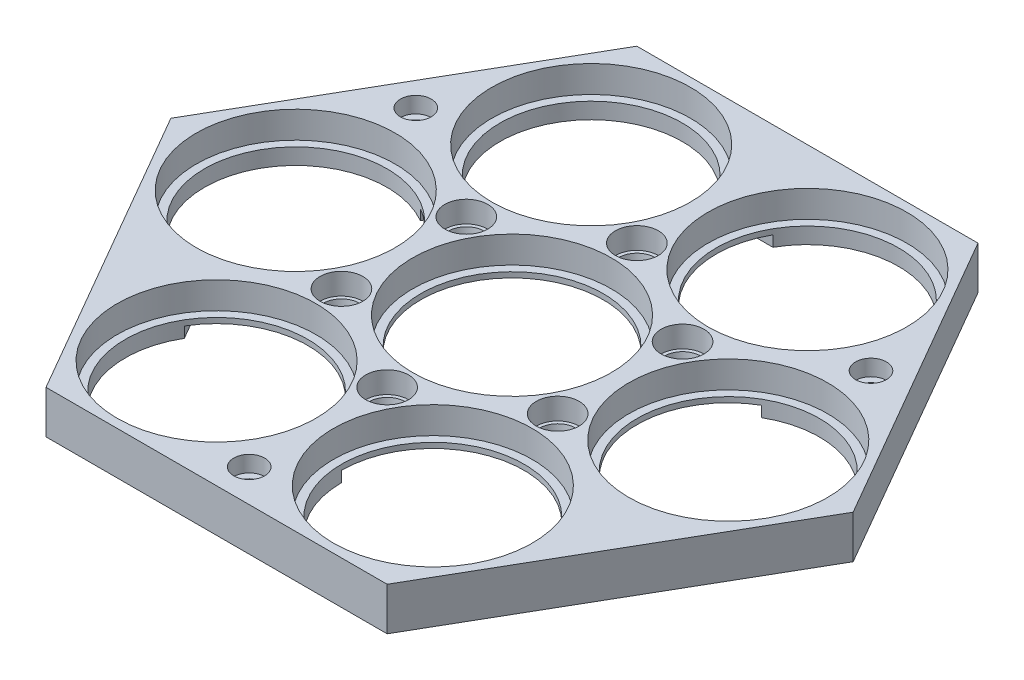
SolidWorks part; units mm, degrees
material "Malleable Cast Iron"
ref_plane "Front Plane" through (0, 0, 0) normal (0, 0, 1) x (1, 0, 0)
ref_plane "Top Plane" through (0, 0, 0) normal (0, 1, 0) x (1, 0, 0)
ref_plane "Right Plane" through (0, 0, 0) normal (1, 0, 0) x (0, 0, -1)
sketch "Sketch1" plane through (0, 0, 0) normal (0, 1, 0) x (1, 0, 0)
  line L0 (-23.3, 0) -> (-17, 0) construction
  line L1 (40.3, 0) -> (20.15, 34.9008) construction
  line L2 (20.15, 34.9008) -> (-20.15, 34.9008) construction
  line L3 (-20.15, 34.9008) -> (-40.3, 0) construction
  line L4 (-40.3, 0) -> (-20.15, -34.9008) construction
  line L5 (-20.15, -34.9008) -> (20.15, -34.9008) construction
  line L6 (20.15, -34.9008) -> (40.3, 0) construction
  line L7 (-20.15, 51.9008) -> (-20.15, 55.0508) construction
  line L8 (63.5672, 0) -> (31.7836, 55.0508)
  line L9 (31.7836, 55.0508) -> (-31.7836, 55.0508)
  line L10 (-31.7836, 55.0508) -> (-63.5672, 0)
  line L11 (-63.5672, 0) -> (-31.7836, -55.0508)
  line L12 (-31.7836, -55.0508) -> (31.7836, -55.0508)
  line L13 (31.7836, -55.0508) -> (63.5672, 0)
  line L14 (-20.15, 0) -> (-17, 0)
  circle A0 centre (0, 0) radius 17
  circle A1 centre (0, 0) radius 34.9008 construction
  circle A2 centre (-20.15, 34.9008) radius 17
  circle A3 centre (20.15, 34.9008) radius 17
  circle A4 centre (40.3, 0) radius 17
  circle A5 centre (20.15, -34.9008) radius 17
  circle A6 centre (-20.15, -34.9008) radius 17
  circle A7 centre (-40.3, 0) radius 17
  circle A8 centre (0, 0) radius 55.0508 construction
  dimension "D1" = 34
  dimension "D2" = 6.3
extrude "Boss-Extrude1" add sketch "Sketch1" along normal blind 1 contours L12 L13 L8 L9 L10 L11 A7 A6 A5 A4 A3 A2 A0 region at (46.2189, 0, 26.6845)
sketch "Sketch2" plane through (0, 1, 0) normal (0, 1, 0) x (1, 0, 0)
  line L1 (63.5672, 0) -> (31.7836, 55.0508)
  line L2 (31.7836, 55.0508) -> (-31.7836, 55.0508)
  line L3 (-31.7836, 55.0508) -> (-63.5672, 0)
  line L4 (-63.5672, 0) -> (-31.7836, -55.0508)
  line L5 (-31.7836, -55.0508) -> (31.7836, -55.0508)
  line L6 (31.7836, -55.0508) -> (63.5672, 0)
  circle A0 centre (-40.3, 0) radius 18.525
  circle A1 centre (-20.15, 34.9008) radius 18.525
  circle A2 centre (20.15, 34.9008) radius 18.525
  circle A3 centre (0, 0) radius 18.525
  circle A4 centre (40.3, 0) radius 18.525
  circle A5 centre (20.15, -34.9008) radius 18.525
  circle A6 centre (-20.15, -34.9008) radius 18.525
  circle A7 centre (0, 0) radius 55.0508 construction
  dimension "D1" = 37.05
extrude "Boss-Extrude2" add sketch "Sketch2" along normal blind 5
sketch "Sketch3" plane through (0, 6, 0) normal (0, 1, 0) x (1, 0, 0)
  line L0 (-24.2569, 9.2625) -> (-20.15, 16.3758) construction
  line L1 (-20.15, 16.3758) -> (-16.0431, 9.2625) construction
  line L2 (-16.0431, 9.2625) -> (-24.2569, 9.2625) construction
  circle A0 centre (-20.15, 11.6336) radius 4
  circle A1 centre (20.15, 11.6336) radius 4
  circle A2 centre (0, -23.2672) radius 4
  circle A3 centre (-20.15, -11.6336) radius 4
  circle A4 centre (20.15, -11.6336) radius 4
  circle A5 centre (0, 0) radius 23.2672 construction
  circle A6 centre (-40.3, 0) radius 18.525 construction
  circle A7 centre (-20.15, 34.9008) radius 18.525 construction
  circle A8 centre (0, 0) radius 18.525 construction
  circle A9 centre (0, 23.2672) radius 4
  dimension "D1" = 120
  dimension "D3" = 8
  dimension "D2" = 120
extrude "Cut-Extrude1" cut sketch "Sketch3" against normal blind 4 and the other way through all
extrude "Cut-Extrude2" cut sketch "Sketch3<2>" against normal through all draft 9 contours A0 | A1 | A2 | A3 | A4 | A9 region at (-20.15, 6, -11.6336) region at (20.15, 6, -11.6336) region at (0, 6, 23.2672) region at (-20.15, 6, 11.6336) region at (20.15, 6, 11.6336) region at (0, 6, -23.2672)
sketch "Sketch3<2>" plane through (0, 6, 0) normal (0, 1, 0) x (1, 0, 0) same geometry as "Sketch3"
sketch "Sketch4" plane through (0, 0, 0) normal (0, -1, 0) x (1, 0, 0)
  circle A0 centre (0, -23.2672) radius 4
  circle A1 centre (-20.15, 11.6336) radius 4
  circle A2 centre (20.15, 11.6336) radius 4
  circle A3 centre (0, 0) radius 23.2672 construction
  point P11 (20.15, -11.6336)
  dimension "D1" = 8
sketch "Sketch5" plane through (0, 0, 0) normal (0, -1, 0) x (1, 0, 0)
  line L0 (-63.5672, 0) -> (-31.7836, -55.0508)
  line L1 (-31.7836, -55.0508) -> (-63.5672, 0) construction
  line L3 (-28.65, -20.1784) -> (-31.8, -14.7224)
  line L4 (-63.5672, 0) -> (-57.3, 0)
  line L5 (-5.3512, -43.2672) -> (5.3512, -43.2672)
  line L6 (31.7836, -55.0508) -> (28.65, -49.6233)
  line L7 (-31.7836, -55.0508) -> (31.7836, -55.0508)
  line L8 (31.7836, 55.0508) -> (-31.7836, 55.0508)
  line L9 (-3.15, 34.9008) -> (3.15, 34.9008)
  line L10 (31.7836, 55.0508) -> (28.65, 49.6233)
  line L11 (-34.7949, 26.2679) -> (-40.1461, 16.9993)
  line L12 (-63.5672, 0) -> (-57.3, 0)
  line L13 (-31.7836, 55.0508) -> (-63.5672, 0)
  line L14 (31.7836, -55.0508) -> (63.5672, 0)
  line L15 (31.8, -14.7224) -> (28.65, -20.1784)
  line L16 (31.7836, -55.0508) -> (28.65, -49.6233)
  line L17 (40.1461, 16.9993) -> (34.7949, 26.2679)
  line L18 (31.7836, 55.0508) -> (28.65, 49.6233)
  line L19 (63.5672, 0) -> (31.7836, 55.0508)
  circle A0 centre (-20.15, -34.9008) radius 17 construction
  circle A2 centre (-40.3, 0) radius 17 construction
  arc A3 (-31.8, -14.7224) -> (-57.3, 0) centre (-40.3, 0) cw
  arc A4 (-5.3512, -43.2672) -> (-28.65, -20.1784) centre (-20.15, -34.9008) cw
  circle A5 centre (20.15, -34.9008) radius 17 construction
  arc A6 (5.3512, -43.2672) -> (28.65, -49.6233) centre (20.15, -34.9008) ccw
  circle A7 centre (0, -23.2672) radius 3.0497 construction
  arc A8 (3.15, 34.9008) -> (28.65, 49.6233) centre (20.15, 34.9008) cw
  arc A9 (-34.7949, 26.2679) -> (-3.15, 34.9008) centre (-20.15, 34.9008) cw
  arc A10 (-40.1461, 16.9993) -> (-57.3, 0) centre (-40.3, 0) ccw
  arc A11 (28.65, -20.1784) -> (28.65, -49.6233) centre (20.15, -34.9008) cw
  arc A12 (40.1461, 16.9993) -> (31.8, -14.7224) centre (40.3, 0) cw
  arc A13 (34.7949, 26.2679) -> (28.65, 49.6233) centre (20.15, 34.9008) ccw
  point P55 (0, 0)
  circle M14 centre (-40.3, 0) radius 17
  circle M15 centre (-20.15, 34.9008) radius 17
  circle M16 centre (20.15, 34.9008) radius 17
  circle M17 centre (40.3, 0) radius 17
  circle M18 centre (20.15, -34.9008) radius 17
  circle M19 centre (-20.15, -34.9008) radius 17
  line M20 (31.7836, 55.0508) -> (-31.7836, 55.0508)
  line M21 (-31.7836, 55.0508) -> (-63.5672, 0)
  line M22 (-63.5672, 0) -> (-31.7836, -55.0508)
  line M23 (-31.7836, -55.0508) -> (31.7836, -55.0508)
  line M24 (31.7836, -55.0508) -> (63.5672, 0)
  line M25 (63.5672, 0) -> (31.7836, 55.0508)
  dimension "D1" = 20
  dimension "D2" = 3
extrude "Boss-Extrude3" add sketch "Sketch5" along normal blind 2 contours L11 L9 L10 L4 M15 M16 M20 M21 M14 | L6 L5 L3 L4 M23 M18 M19 M14 M22 | L17 L15 L6 L10 M17 M18 M24 M25 M16 region at (-60.4336, 0, -1.101) region at (-46.7219, 0, 26.9749) region at (31.2171, 0, -51.7595)
sketch "Sketch6" plane through (0, 0, 0) normal (0, 1, 0) x (1, 0, 0)
  line L1 (36.7588, -6.1336) -> (3.5412, -6.1336)
  line L2 (3.5412, -6.1336) -> (-13.0675, -34.9008)
  line L3 (-13.0675, -34.9008) -> (3.5412, -63.668)
  line L4 (3.5412, -63.668) -> (36.7588, -63.668)
  line L5 (36.7588, -63.668) -> (53.3675, -34.9008)
  line L6 (53.3675, -34.9008) -> (36.7588, -6.1336)
  circle A0 centre (20.15, -34.9008) radius 28.7672 construction
  circle A1 centre (20.15, -11.6336) radius 4 construction
  dimension "D1" = 5.5
extrude "Cut-Extrude3" [suppressed] cut sketch "Sketch6" against normal through all both and the other way through all flip side to cut
sketch "Sketch7" plane through (0, 6, 0) normal (0, 1, 0) x (1, 0, 0)
  line L0 (-42.4095, 24.4851) -> (-37.1435, 27.5254) construction
  line L1 (-42.4095, 24.4851) -> (-42.4095, 18.4045) construction
  line L2 (-42.4095, 24.4851) -> (-47.6754, 27.5254) construction
  line L3 (-31.7836, 55.0508) -> (-63.5672, 0) construction
  line L4 (42.4095, 24.4851) -> (42.4095, 18.4045) construction
  line L5 (42.4095, 24.4851) -> (37.1435, 27.5254) construction
  line L6 (42.4095, 24.4851) -> (47.6754, 27.5254) construction
  line L7 (0, -48.9702) -> (-5.266, -45.9299) construction
  line L8 (0, -48.9702) -> (5.266, -45.9299) construction
  line L9 (0, -48.9702) -> (0, -55.0508) construction
  circle A0 centre (-42.4095, 24.4851) radius 2.875
  circle A1 centre (-20.15, 34.9008) radius 18.525 construction
  circle A2 centre (-40.3, 0) radius 18.525 construction
  circle A3 centre (-42.4095, 24.4851) radius 1.55
  circle A4 centre (-20.15, 34.9008) radius 18.525 construction
  circle A5 centre (42.4095, 24.4851) radius 2.875
  circle A6 centre (42.4095, 24.4851) radius 1.55
  circle A7 centre (0, -48.9702) radius 2.875
  circle A8 centre (0, -48.9702) radius 1.55
  point P33 (0, 0)
  dimension "D1" = 5.75
  dimension "D2" = 3.1
  dimension "D3" = 3
extrude "Cut-Extrude4" cut sketch "Sketch7" against normal through all contours A3 | A6 | A8 region at (-42.4095, 6, -24.4851)
extrude "Cut-Extrude5" cut sketch "Sketch7<3>" against normal blind 3 contours A0 A3 | A5 | A7 region at (-45.2031, 6, -24.4851)
sketch "Sketch7<3>" plane through (0, 6, 0) normal (0, 1, 0) x (1, 0, 0) same geometry as "Sketch7"
